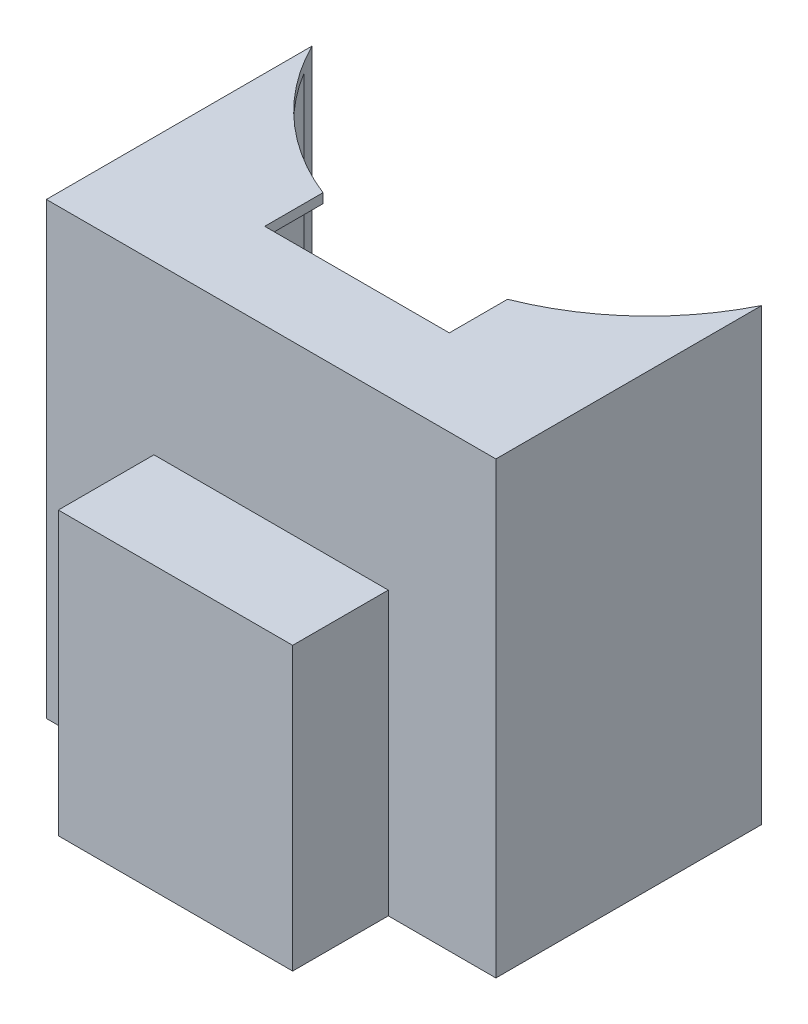
SolidWorks part; units mm, degrees
material "PLA"
ref_plane "Front Plane" through (0, 0, 0) normal (0, 0, 1) x (1, 0, 0)
ref_plane "Top Plane" through (0, 0, 0) normal (0, 1, 0) x (1, 0, 0)
ref_plane "Right Plane" through (0, 0, 0) normal (1, 0, 0) x (0, 0, -1)
sketch "Esquisse1" plane through (0, 0, 0) normal (0, 1, 0) x (1, 0, 0)
  line L0 (0, 0) -> (-30, -51.9615) construction
  line L1 (0, 0) -> (30, -51.9615) construction
  line L2 (-40, -66.9615) -> (40, -66.9615) construction
  line L3 (-30, -51.9615) -> (30, -51.9615) construction
  circle A0 centre (0, 0) radius 52.5 construction
  point P5 (0, -66.9615)
  point P9 (0, -51.9615)
  dimension "D4" = 105
  dimension "D1" = 60
  dimension "D2" = 15
  dimension "D3" = 60
  dimension "D5" = 80
ref_plane "Plan4" through (0, 90, 0) normal (0, 1, 0) x (1, 0, 0)
sketch "Esquisse2" plane through (0, 90, 0) normal (0, 1, 0) x (1, 0, 0)
  line L0 (-40, -66.9615) -> (40, -66.9615) construction
ref_plane "Plan5" through (0, 0, 66.9615) normal (0, 0, -1) x (-1, 0, 0)
sketch "Esquisse3" plane through (0, 0, 66.9615) normal (0, 0, -1) x (-1, 0, 0)
  line L0 (40, 90) -> (-40, 90) construction
  line L1 (40, 5) -> (-40, 5) construction
  line L2 (40, 5) -> (40, 85) construction
  line L3 (40, 85) -> (-40, 85) construction
  line L4 (-40, 5) -> (-40, 85) construction
  line L5 (47, 92) -> (47, -2)
  line L6 (47, 92) -> (-47, 92)
  line L7 (-47, 92) -> (-47, -2)
  line L8 (-47, -2) -> (47, -2)
  line L9 (22.5, -2) -> (22.5, 55)
  line L10 (22.5, 55) -> (-22.5, 55)
  line L11 (-22.5, 55) -> (-22.5, -2)
  line L12 (-24.5, -2) -> (-24.5, 57)
  line L13 (-24.5, 57) -> (24.5, 57)
  line L14 (24.5, 57) -> (24.5, -2)
  line L15 (22.5, 55) -> (24.5, 55) construction
  line L16 (-22.5, 55) -> (-24.5, 55) construction
  line L17 (0, 55) -> (0, 57) construction
  line L19 (19.7, 24.1) -> (3.2, 24.1) construction
  line L20 (19.7, 24.1) -> (19.7, 49.9) construction
  line L21 (19.7, 49.9) -> (3.2, 49.9) construction
  line L22 (3.2, 24.1) -> (3.2, 49.9) construction
  line L23 (-3.3, 24.1) -> (-19.8, 24.1) construction
  line L24 (-3.3, 24.1) -> (-3.3, 49.9) construction
  line L25 (-3.3, 49.9) -> (-19.8, 49.9) construction
  line L26 (-19.8, 24.1) -> (-19.8, 49.9) construction
  point P6 (0, 90)
  point P7 (0, 85)
  point P32 (0, 92)
  dimension "D1" = 80
  dimension "D2" = 5
  dimension "D3" = 20.3
  dimension "D4" = 16.5
  dimension "D5" = 6.5
  dimension "D6" = 19.1
  dimension "D7" = 25.8
  dimension "D8" = 50
  dimension "D9" = 45
  dimension "D10" = 2
  dimension "D11" = 7
  dimension "D12" = 7
  dimension "D13" = 7
extrude "Boss.-Extru.1" add sketch "Esquisse3" against normal blind 2 from offset 10 contours L13 L14 L8 L5 L6 L7 L12 | L14 L13 L12 L8 L11 L10 L9 region at (-45.6706, 45, 66.9615) region at (-23.5, -1.2331, 66.9615) offset against normal yes
extrude "Boss.-Extru.2" add sketch "Esquisse3<3>" against normal blind 20 from surface contours L14 L13 L12 L8 L11 L10 L9 region at (-23.5, -1.2331, 66.9615) starting at face at (0, 35.75, 78.9615)
sketch "Esquisse3<3>" plane through (0, 0, 66.9615) normal (0, 0, -1) x (-1, 0, 0) same geometry as "Esquisse3"
extrude "Boss.-Extru.3" add sketch "Esquisse3<4>" along normal blind 2 from surface contours L10 L11 L8 L9 region at (0, 26.5, 66.9615) starting at face at (0, 27, 98.9615)
sketch "Esquisse3<4>" plane through (0, 0, 66.9615) normal (0, 0, -1) x (-1, 0, 0) same geometry as "Esquisse3"
sketch "Esquisse4" plane through (0, 92, 0) normal (0, 1, 0) x (1, 0, 0)
  line L0 (-47, -76.9615) -> (-47, -23.3934)
  line L1 (-45, -76.9615) -> (-45, -27.0416)
  line L2 (-47, -76.9615) -> (47, -76.9615) construction
  line L3 (47, -76.9615) -> (47, -23.3934)
  line L4 (45, -76.9615) -> (45, -27.0416)
  line L5 (47, -76.9615) -> (45, -76.9615)
  line L6 (-47, -76.9615) -> (-45, -76.9615)
  line L7 (-19.3, -61.0015) -> (19.3, -61.0015)
  line L8 (-40, -66.9615) -> (40, -66.9615) construction
  line L9 (-19.3, -61.0015) -> (-19.3, -48.8238)
  line L10 (19.3, -61.0015) -> (19.3, -48.8238)
  circle A0 centre (0, 0) radius 52.5 construction
  arc A1 (-47, -23.3934) -> (-45, -27.0416) centre (0, 0) ccw
  arc A2 (47, -23.3934) -> (45, -27.0416) centre (0, 0) cw
  arc A3 (-45, -27.0416) -> (-19.3, -48.8238) centre (0, 0) ccw
  arc A4 (19.3, -48.8238) -> (45, -27.0416) centre (0, 0) ccw
  point P20 (0, -61.0015)
  point P25 (0, 0)
  line M5 (47, -76.9615) -> (-47, -76.9615)
  dimension "D1" = 2
  dimension "D2" = 5.96
  dimension "D3" = 38.6
extrude "Boss.-Extru.4" add sketch "Esquisse4" against normal blind 2 contours A4 L10 L7 L9 A3 L1 L4 M5 region at (-43.9708, 92, 52.0016)
extrude "Boss.-Extru.5" add sketch "Esquisse4<3>" against normal up to surface (94 mm away) contours L3 A2 L4 M5 | A1 L0 L6 L1 region at (46.0117, 92, 51.1074) up to face at (0, -2, 84.6282)
sketch "Esquisse4<3>" plane through (0, 92, 0) normal (0, 1, 0) x (1, 0, 0) same geometry as "Esquisse4"
